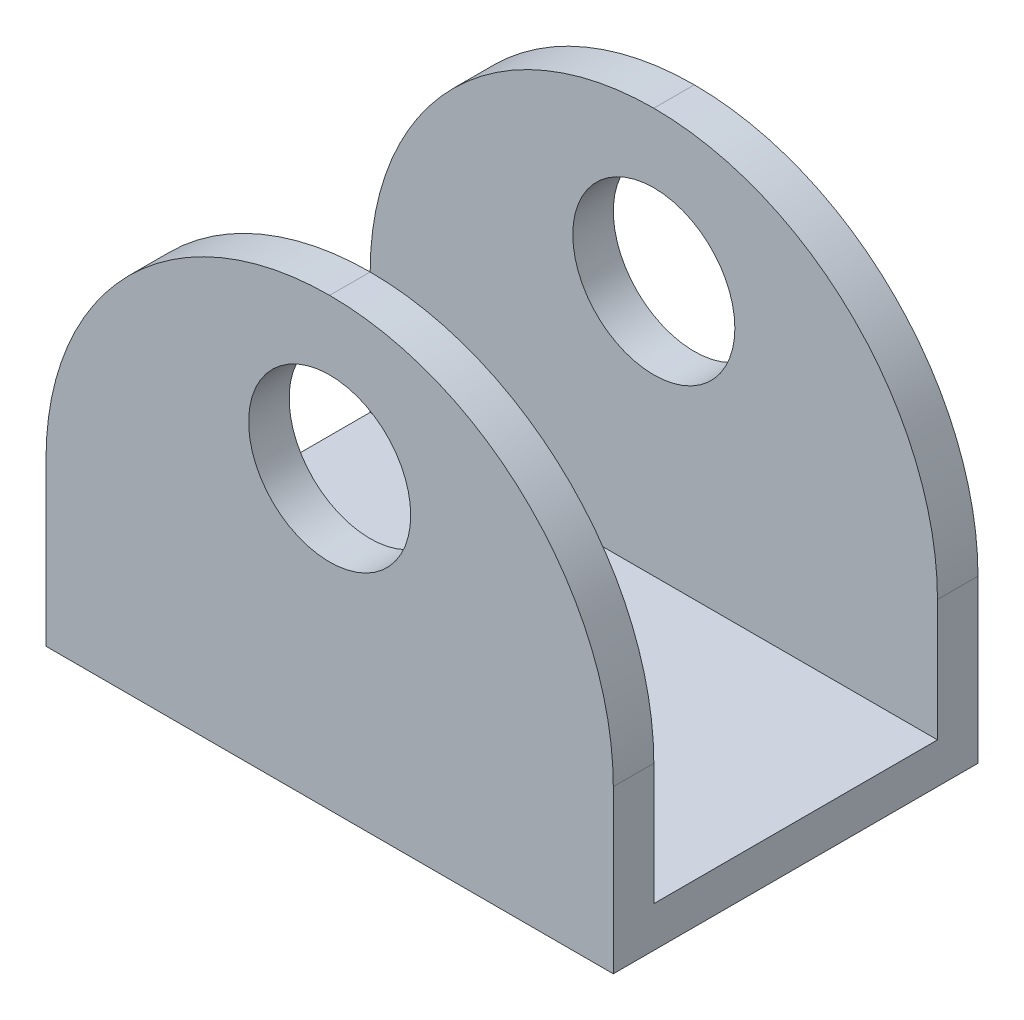
SolidWorks part; units mm, degrees
ref_plane "Alzado" through (0, 0, 0) normal (0, 0, 1) x (1, 0, 0)
ref_plane "Planta" through (0, 0, 0) normal (0, 1, 0) x (1, 0, 0)
ref_plane "Vista lateral" through (0, 0, 0) normal (1, 0, 0) x (0, 0, -1)
sketch "Croquis1" plane through (0, 0, 0) normal (0, 1, 0) x (1, 0, 0)
  line L1 (-70, 45) -> (70, 45)
  line L2 (-70, 45) -> (-70, -45)
  line L3 (-70, -45) -> (70, -45)
  line L4 (70, 45) -> (70, -45)
  line L5 (-70, 45) -> (70, -45) construction
  line L6 (-70, -45) -> (70, 45) construction
  point P0 (0, 0)
  dimension "D1" = 140
  dimension "D2" = 90
extrude "Saliente-Extruir1" add sketch "Croquis1" along normal blind 10
sketch "Croquis2" plane through (0, 10, 0) normal (0, 1, 0) x (1, 0, 0)
  line L0 (70, -45) -> (-70, -45)
  line L1 (70, -45) -> (70, -35)
  line L2 (-70, -45) -> (-70, -35)
  line L3 (70, -35) -> (-70, -35)
  line L4 (70, 45) -> (-70, 45)
  line L5 (70, 45) -> (70, 35)
  line L6 (-70, 45) -> (-70, 35)
  line L7 (70, 35) -> (-70, 35)
  dimension "D1" = 10
  dimension "D2" = 10
extrude "Saliente-Extruir2" add sketch "Croquis2" along normal blind 100
fillet "Redondeo1" radius 70 4 edges at (-70, 110, 40) (70, 110, 40) (70, 110, -40) (-70, 110, -40)
sketch "Croquis3" plane through (0, 0, 45) normal (0, 0, 1) x (1, 0, 0)
  line L0 (0, 0) -> (0, 110)
  line L1 (-70, 0) -> (70, 0) construction
  line L2 (0, 110) -> (0, 73)
  arc A0 (70, 40) -> (0, 110) centre (0, 40) ccw construction
  circle A1 centre (0, 73) radius 20
extrude "Cortar-Extruir1" cut sketch "Croquis3" against normal blind 100 contours L0 A1 | L0 A1 region at (-8.4883, 73, 45) region at (8.4883, 73, 45)
